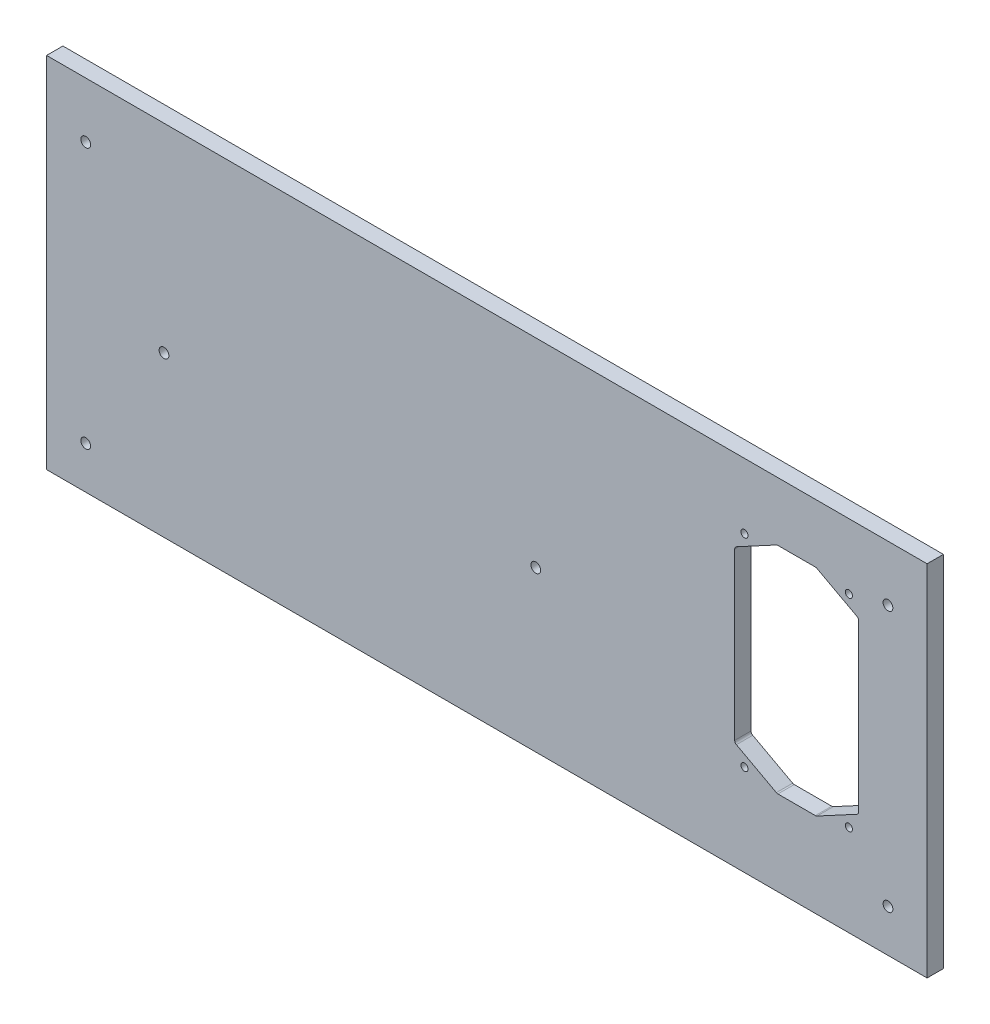
SolidWorks part; units mm, degrees
material "Acrylic (Medium-high impact)"
ref_plane "Front Plane" through (0, 0, 0) normal (0, 0, 1) x (1, 0, 0)
ref_plane "Top Plane" through (0, 0, 0) normal (0, 1, 0) x (1, 0, 0)
ref_plane "Right Plane" through (0, 0, 0) normal (1, 0, 0) x (0, 0, -1)
sketch "Sketch1" plane through (0, 0, 0) normal (0, 0, 1) x (1, 0, 0)
  line L1 (135, -55) -> (-135, -55)
  line L2 (135, -55) -> (135, 55)
  line L3 (135, 55) -> (-135, 55)
  line L4 (-135, -55) -> (-135, 55)
  line L5 (135, -55) -> (-135, 55) construction
  line L6 (135, 55) -> (-135, -55) construction
  point P0 (0, 0)
  dimension "D1" = 110
  dimension "D2" = 270
extrude "Base" add sketch "Sketch1" along normal mid plane 5
sketch "Sketch2" plane through (0, 0, 2.5) normal (0, 0, 1) x (1, 0, 0)
  line L0 (135, -55) -> (135, 55) construction
  line L1 (-135, -55) -> (135, -55) construction
  line L2 (-135, 55) -> (-135, -55) construction
  line L3 (135, 55) -> (-135, 55) construction
  circle A0 centre (-123, -42) radius 1.5
  circle A2 centre (123, -42) radius 1.5
  circle A3 centre (123, 38) radius 1.5
  circle A4 centre (-123, 38) radius 1.5
  dimension "D1" = 12
  dimension "D5" = 3
  dimension "D2" = 13
  dimension "D4" = 12
  dimension "D6" = 17
extrude "MountHoles" cut sketch "Sketch2" against normal through all
sketch "Sketch3" plane through (0, 0, -2.5) normal (0, 0, -1) x (-1, 0, 0)
  line L0 (-135, -55) -> (-135, 55) construction
  line L1 (135, -55) -> (-135, -55) construction
  circle A0 centre (-15, -6) radius 1.5
  circle A1 centre (99, -6) radius 1.5
  dimension "D4" = 3
  dimension "D1" = 114
  dimension "D2" = 120
  dimension "D3" = 49
extrude "MiddlePartHoles" cut sketch "Sketch3" against normal through all
chamfer "ChamferAll" distance 1.7 angle 45 6 edges at (-121.5, -42, -2.5) (124.5, -42, -2.5) (-121.5, 38, -2.5) (124.5, 38, -2.5) (-100.5, -6, -2.5) (13.5, -6, -2.5)
sketch "Sketch4" plane through (0, 0, -2.5) normal (0, 0, -1) x (-1, 0, 0)
  line L0 (-101, 37) -> (-114, 30)
  line L1 (-89, -29) -> (-101, -29)
  line L2 (-76, -22) -> (-76, 30)
  line L3 (-89, 37) -> (-101, 37)
  line L4 (-114, -22) -> (-114, 30)
  line L5 (-76, -29) -> (-114, 37) construction
  line L6 (-76, 37) -> (-114, -29) construction
  line L7 (-79, -27) -> (-111, -27) construction
  line L8 (-79, -27) -> (-79, 35) construction
  line L9 (-79, 35) -> (-111, 35) construction
  line L10 (-111, -27) -> (-111, 35) construction
  line L11 (-79, -27) -> (-111, 35) construction
  line L12 (-79, 35) -> (-111, -27) construction
  line L13 (-101, -29) -> (-114, -22)
  line L14 (-95, 4) -> (-95, 17.8562) construction
  line L15 (-76, 30) -> (-89, 37)
  line L16 (-76, -22) -> (-89, -29)
  line L17 (-135, -55) -> (-135, 55) construction
  line L18 (135, -55) -> (-135, -55) construction
  circle A0 centre (-79, 35) radius 1.1
  circle A1 centre (-111, 35) radius 1.1
  circle A2 centre (-111, -27) radius 1.1
  circle A3 centre (-79, -27) radius 1.1
  point P0 (-95, 4)
  point P14 (-95, 4)
  dimension "D1" = 2.2
  dimension "D2" = 62
  dimension "D3" = 32
  dimension "D4" = 38
  dimension "D5" = 66
  dimension "D6" = 13
  dimension "D7" = 7
  dimension "D8" = 13
  dimension "D9" = 7
  dimension "D10" = 7
  dimension "D11" = 13
  dimension "D12" = 13
  dimension "D13" = 7
  dimension "D14" = 40
  dimension "D15" = 59
extrude "Cut-Extrude1" cut sketch "Sketch4" against normal through all
fillet "Fillet1" radius 1 8 edges at (76, 30, 0) (89, -29, 0) (101, -29, 0) (114, -22, 0) (114, 30, 0) (101, 37, 0) (89, 37, 0) (76, -22, 0)
